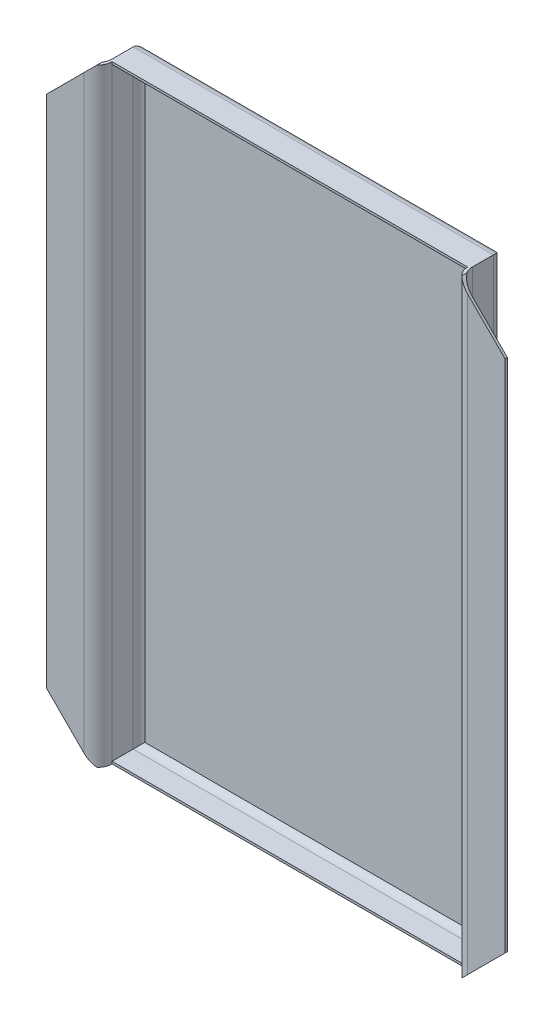
SolidWorks part; units mm, degrees
ref_plane "Front Plane" through (0, 0, 0) normal (0, 0, 1) x (1, 0, 0)
ref_plane "Top Plane" through (0, 0, 0) normal (0, 1, 0) x (1, 0, 0)
ref_plane "Right Plane" through (0, 0, 0) normal (1, 0, 0) x (0, 0, -1)
sketch "Sketch1" plane through (0, 0, 0) normal (0, 0, 1) x (1, 0, 0)
  line L1 (-38.5, 65) -> (38.5, 65)
  line L2 (-38.5, 65) -> (-38.5, -65)
  line L3 (-38.5, -65) -> (38.5, -65)
  line L4 (38.5, 65) -> (38.5, -65)
  line L5 (-38.5, 65) -> (38.5, -65) construction
  line L6 (-38.5, -65) -> (38.5, 65) construction
  point P0 (0, 0)
  dimension "D1" = 77
  dimension "D2" = 130
extrude "Boss-Extrude1" add sketch "Sketch1" along normal blind 10
sketch "Sketch2" plane through (38.5, 0, 0) normal (1, 0, 0) x (0, 0, -1)
  line L0 (-10, -65) -> (0, -65) construction
  line L1 (-10, 65) -> (-9.5, 65)
  line L2 (-10, 65) -> (-10, -65)
  line L3 (-10, -65) -> (-9.5, -65)
  line L4 (-9.5, 65) -> (-9.5, -65)
  dimension "D1" = 0.5
extrude "Boss-Extrude2" add sketch "Sketch2" along normal blind 10.5
chamfer "Chamfer1" distance 10 angle 45 2 edges at (49, -65, 9.75) (49, 65, 9.75)
mirror "Mirror1" about plane through (0, 0, 0) normal (1, 0, 0) of "Chamfer1", "Boss-Extrude2"
shell "Shell1" thickness 0.5 removed face at (0, 0, 10)
fillet "Fillet1" radius 2 8 edges at (0, 65, 0) (-38.5, 0, 0) (0, -65, 0) (38.5, 0, 0) (0, -64.5, 0.5) (-38, 0, 0.5) (0, 64.5, 0.5) (38, 0, 0.5)
fillet "Fillet2" radius 3 4 edges at (38, 0, 10) (-38, 0, 10) (-38.5, 0, 9.5) (38.5, 0, 9.5)
sketch "Sketch3" plane through (0, -64.5, 0) normal (0, 1, 0) x (1, 0, 0)
  line L0 (-38, -7) -> (38, -7)
  line L6 (-39.5, -10) -> (39.5, -10)
  line L7 (39.5, -10) -> (39.5, -9.5981)
  line L8 (38, -7) -> (38, -2.5)
  line L9 (38, -2.5) -> (-38, -2.5)
  line L10 (-38, -2.5) -> (-38, -7)
  line L11 (-39.5, -9.5981) -> (-39.5, -10)
  line L12 (-39.5, -10) -> (39.5, -10)
  line L13 (39.5, -10) -> (39.5, -9.5981)
  line L17 (-39.5, -9.5981) -> (-39.5, -10)
  arc A2 (38, -7) -> (39.5, -9.5981) centre (41, -7) ccw
  arc A3 (-39.5, -9.5981) -> (-38, -7) centre (-41, -7) ccw
  arc A4 (38, -7) -> (39.5, -9.5981) centre (41, -7) ccw
  arc A5 (-39.5, -9.5981) -> (-38, -7) centre (-41, -7) ccw
  dimension "D1" = 0
extrude "Cut-Extrude1" cut sketch "Sketch3" against normal mid plane 270.5
sketch "Sketch4" plane through (0, 0, 0.5) normal (0, 0, 1) x (1, 0, 0)
  line L8 (-36.5, 63) -> (-36.5, -63)
  line L9 (-36.5, -63) -> (36.5, -63)
  line L10 (36.5, -63) -> (36.5, 63)
  line L11 (36.5, 63) -> (-36.5, 63)
  line L12 (-36.5, 63) -> (-36.5, -63)
  line L13 (-36.5, -63) -> (36.5, -63)
  line L14 (36.5, -63) -> (36.5, 63)
  line L15 (36.5, 63) -> (-36.5, 63)
  dimension "D1" = 0.5
extrude "Boss-Extrude3" add sketch "Sketch4" along normal blind 1 separate body
